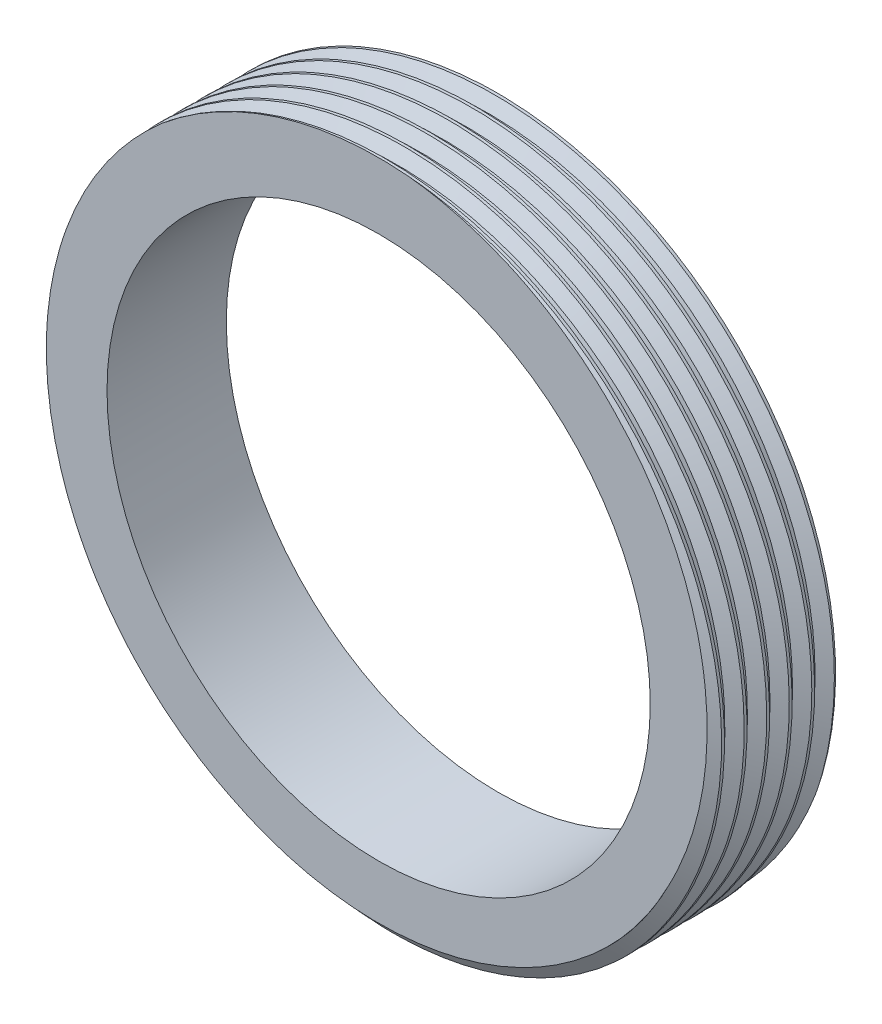
SolidWorks part; units mm, degrees
ref_plane "Plan de face" through (0, 0, 0) normal (0, 0, 1) x (1, 0, 0)
ref_plane "Plan de dessus" through (0, 0, 0) normal (0, 1, 0) x (1, 0, 0)
ref_plane "Plan de droite" through (0, 0, 0) normal (1, 0, 0) x (0, 0, -1)
sketch "Esquisse1" plane through (0, 0, 0) normal (0, 0, 1) x (1, 0, 0)
  circle A0 centre (0, 0) radius 15.85
extrude "Boss.-Extru.1" add sketch "Esquisse1" along normal blind 5.6
thread "Filetage1" pitch 1.0583 method cut profile "Profil de filetage2" start angle 0, offset 1, length 0, pitch 1.0583, diameter 31.7
ref_plane "Plan2" through (15.85, 0, -1) normal (0, -1, 0) x (1, 0, 0)
sketch "Profil de filetage2" plane through (15.85, 0, -1) normal (0, -1, 0) x (1, 0, 0)
  line L0 (0, 0) -> (0, 1.0583) construction
  line L11 (0, 0) -> (0, 0.926)
  line L12 (0, 0.926) -> (-0.5728, 0.5953)
  line L13 (-0.5728, 0.5953) -> (-0.5728, 0.3307)
  line L15 (-0.5728, 0.3307) -> (0, 0)
  line L17 (-0.5728, 0.463) -> (0, 0.463) construction
  point P2 (0, 0)
  dimension "Pitch" = 1.0583
  dimension "Profile_Angle" = 60
  dimension "Profile_Land" = 0.2646
  dimension "Profile_Height" = 0.5728
sketch "Esquisse23" plane through (0, 0, 0) normal (0, 0, -1) x (-1, 0, 0)
  circle A0 centre (0, 0) radius 12.75
extrude "Enlèv. mat.-Extru.1" cut sketch "Esquisse23" against normal blind 10
